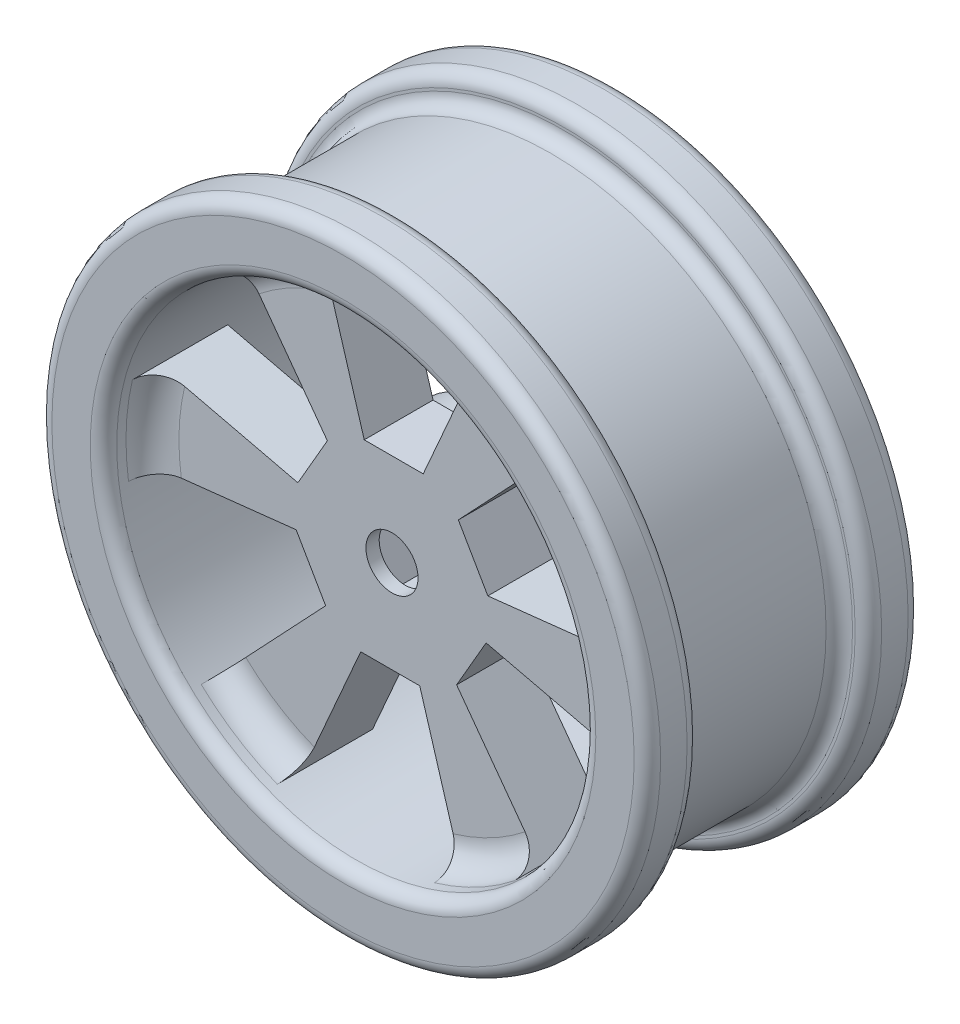
SolidWorks part; units mm, degrees
material "ABS"
ref_plane "Front Plane" through (0, 0, 0) normal (0, 0, 1) x (1, 0, 0)
ref_plane "Top Plane" through (0, 0, 0) normal (0, 1, 0) x (1, 0, 0)
ref_plane "Right Plane" through (0, 0, 0) normal (1, 0, 0) x (0, 0, -1)
sketch "Sketch1" plane through (0, 0, 0) normal (1, 0, 0) x (0, 0, -1)
  line L0 (0, 0) -> (59.5506, 0) construction
  line L1 (0, 0) -> (0, 22.987) construction
  line L2 (0, 22.987) -> (15.24, 22.987) construction
  line L3 (17.78, 25.527) -> (17.78, 27.94)
  line L4 (16.51, 29.21) -> (13.97, 29.21)
  line L5 (12.7, 27.94) -> (12.7, 27.686)
  line L6 (11.43, 26.416) -> (-2.159, 26.416)
  line L7 (-3.429, 27.686) -> (-3.429, 27.94)
  line L8 (-4.699, 29.21) -> (-7.239, 29.21)
  line L9 (-8.509, 27.94) -> (-8.509, 24.257)
  line L10 (-7.239, 22.987) -> (-6.35, 22.987)
  line L11 (-3.81, 20.447) -> (-3.81, 0)
  line L12 (-3.81, 0) -> (0, 0)
  line L13 (2.794, 22.987) -> (15.24, 22.987)
  line L14 (2.794, 22.987) -> (2.794, 8.4709)
  line L15 (2.794, 8.4709) -> (5.715, 8.4709)
  line L16 (5.715, 8.4709) -> (5.715, 0)
  line L17 (5.715, 0) -> (0, 0)
  arc A0 (-6.35, 22.987) -> (-3.81, 20.447) centre (-6.35, 20.447) cw
  arc A1 (16.51, 29.21) -> (17.78, 27.94) centre (16.51, 27.94) cw
  arc A2 (13.97, 29.21) -> (12.7, 27.94) centre (13.97, 27.94) ccw
  arc A3 (-7.239, 29.21) -> (-8.509, 27.94) centre (-7.239, 27.94) ccw
  arc A4 (-4.699, 29.21) -> (-3.429, 27.94) centre (-4.699, 27.94) cw
  arc A5 (12.7, 27.686) -> (11.43, 26.416) centre (11.43, 27.686) cw
  arc A6 (-3.429, 27.686) -> (-2.159, 26.416) centre (-2.159, 27.686) ccw
  arc A7 (-7.239, 22.987) -> (-8.509, 24.257) centre (-7.239, 24.257) cw
  arc A8 (17.78, 25.527) -> (15.24, 22.987) centre (15.24, 25.527) cw
  point P22 (12.7, 29.21)
  point P29 (12.7, 26.416)
  point P36 (17.78, 22.987)
  dimension "D8" = 2.54
  dimension "D9" = 1.27
  dimension "D10" = 2.54
  dimension "D11" = 45.974
  dimension "D1" = 58.42
  dimension "D2" = 2.794
  dimension "D3" = 14.986
  dimension "D4" = 5.08
  dimension "D5" = 3.81
  dimension "D6" = 26.289
  dimension "D7" = 17.78
  dimension "D12" = 16.9418
  dimension "D13" = 12.065
revolve "Body" add sketch "Sketch1" angle 360 about L0
sketch "Sketch2" plane through (0, 0, 0) normal (0, 0, 1) x (1, 0, 0)
  line L0 (-2.6636, 8.89) -> (2.9969, 8.89)
  line L1 (3.3042, -6.0895) -> (6.9258, -0.1832)
  line L2 (6.9258, -0.1832) -> (3.6216, 5.9063)
  line L3 (3.6216, 5.9063) -> (-3.3042, 6.0895)
  line L4 (-3.3042, 6.0895) -> (-6.9258, 0.1832)
  line L5 (-6.9258, 0.1832) -> (-3.6216, -5.9063)
  line L6 (-3.6216, -5.9063) -> (3.3042, -6.0895)
  line L7 (2.9969, 8.89) -> (8.47, 21.3696)
  line L8 (-2.6636, 8.89) -> (-6.5976, 22.0199)
  circle A0 centre (0, 0) radius 6 construction
  circle A1 centre (0, 0) radius 22.987 construction
  arc A2 (-6.5976, 22.0199) -> (8.47, 21.3696) centre (0, 0) cw
  circle A3 centre (0, 0) radius 2.5
  circle A4 centre (0, 0) radius 6.9282 construction
  dimension "D1" = 5
  dimension "D2" = 12
  dimension "D3" = 8.89
extrude "Nut" cut sketch "Sketch2" against normal blind 8.89 and the other way blind 2.54 contours L2 L3 L4 L5 L6 L1
extrude "Spokes" cut sketch "Sketch2<3>" against normal through all both and the other way through all contours L7 A2 L8 L0
sketch "Sketch2<3>" plane through (0, 0, 0) normal (0, 0, 1) x (1, 0, 0) same geometry as "Sketch2"
pattern_circular "CirPattern1" count 6 over 360 about axis through (0, 0, 0) along (0, 0, 1) of "Spokes"
extrude "Axle" cut sketch "Sketch2<4>" along normal through all both and the other way through all contours A3
sketch "Sketch2<4>" plane through (0, 0, 0) normal (0, 0, 1) x (1, 0, 0) same geometry as "Sketch2"
